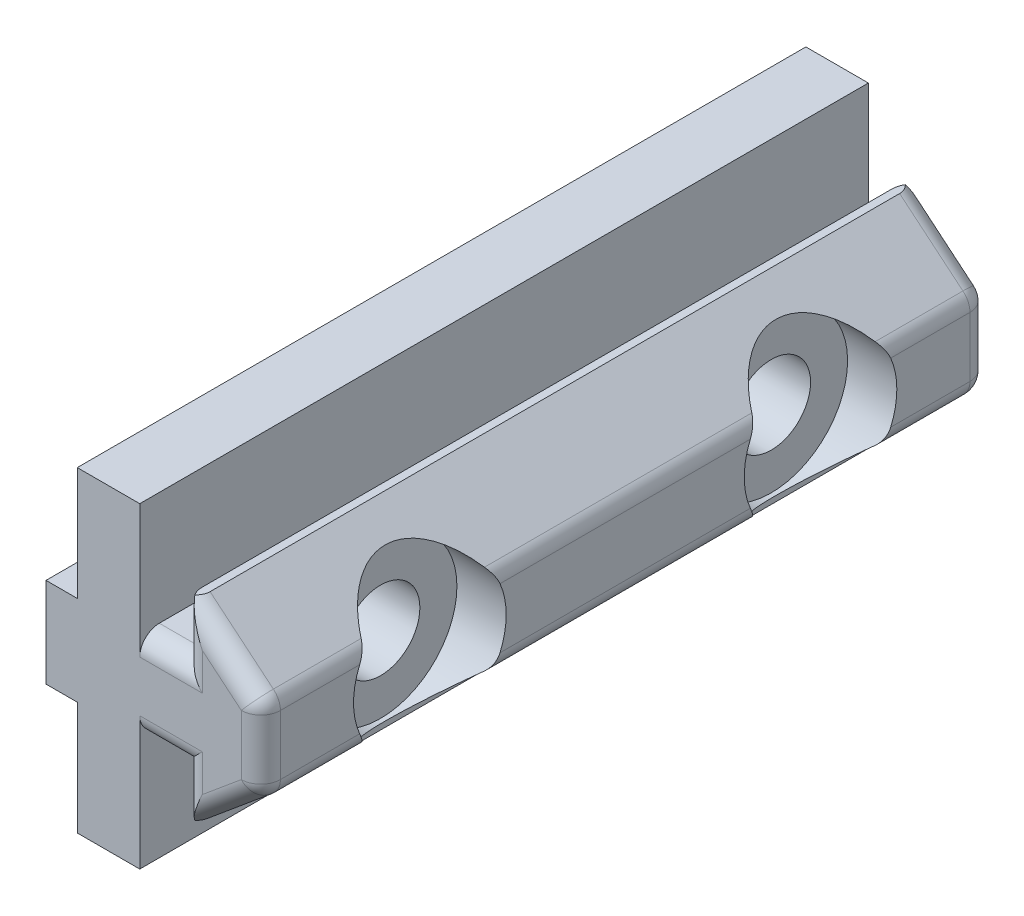
SolidWorks part; units mm, degrees
ref_plane "Front Plane" through (0, 0, 0) normal (0, 0, 1) x (1, 0, 0)
ref_plane "Top Plane" through (0, 0, 0) normal (0, 1, 0) x (1, 0, 0)
ref_plane "Right Plane" through (0, 0, 0) normal (1, 0, 0) x (0, 0, -1)
ref_plane "Plane1" through (0, 0, 23.6855) normal (0, 0, 1) x (1, 0, 0)
sketch "Sketch1" plane through (0, 0, 23.6855) normal (0, 0, 1) x (1, 0, 0)
  line L0 (3.302, 6.35) -> (-4.064, 6.35)
  line L1 (-4.064, 6.35) -> (-4.064, -6.35)
  line L2 (-4.064, -6.35) -> (3.302, -6.35)
  line L3 (3.302, -6.35) -> (7.874, -2.54)
  line L4 (7.874, -2.54) -> (7.874, 2.54)
  line L5 (7.874, 2.54) -> (3.302, 6.35)
extrude "Boss-Extrude1" add sketch "Sketch1" against normal blind 47.371
sketch "Sketch2" plane through (0, 0, 23.6855) normal (0, 0, 1) x (1, 0, 0)
  line L0 (-4.064, 6.35) -> (-4.064, 2.921)
  line L1 (-4.064, 2.921) -> (2.794, 2.921)
  line L2 (2.794, 2.921) -> (2.794, 6.35)
  line L3 (2.794, 6.35) -> (-4.064, 6.35)
extrude "Cut-Extrude1" cut sketch "Sketch2" against normal through all
sketch "Sketch3" plane through (0, 2.921, 0) normal (0, 1, 0) x (-1, 0, 0)
  line L0 (4.064, -23.6855) -> (0, -23.6855)
  line L1 (0, -23.6855) -> (0, 23.6855)
  line L2 (0, 23.6855) -> (4.064, 23.6855)
  line L3 (4.064, 23.6855) -> (4.064, -23.6855)
extrude "Boss-Extrude2" add sketch "Sketch3" along normal blind 7.366
sketch "Sketch4" plane through (0, 0, 23.6855) normal (0, 0, 1) x (1, 0, 0)
  line L0 (-4.064, -6.35) -> (2.794, -6.35)
  line L1 (2.794, -6.35) -> (2.794, -2.921)
  line L2 (2.794, -2.921) -> (-4.064, -2.921)
  line L3 (-4.064, -2.921) -> (-4.064, -6.35)
extrude "Cut-Extrude2" cut sketch "Sketch4" against normal through all
sketch "Sketch5" plane through (0, -2.921, 0) normal (0, -1, 0) x (1, 0, 0)
  line L0 (0, -23.6855) -> (-4.064, -23.6855)
  line L1 (-4.064, -23.6855) -> (-4.064, 23.6855)
  line L2 (-4.064, 23.6855) -> (0, 23.6855)
  line L3 (0, 23.6855) -> (0, -23.6855)
extrude "Boss-Extrude3" add sketch "Sketch5" along normal blind 7.366
hole_wizard "#3 Clearance Hole1" positions "Sketch7" profile "Sketch6" hole size "#3" standard "ANSI Inch"
sketch "Sketch7" plane through (-4.064, 0, 0) normal (-1, 0, 0) x (0, 0, 1)
  point P0 (12.7, 0)
  point P1 (-12.7, 0)
sketch "Sketch6" plane through (-4.064, 0, 12.7) normal (0, 1, 0) x (0, 0, 1)
  line L0 (0, 0) -> (0, 11.938)
  line L1 (0, 11.938) -> (1.3843, 11.938)
  line L2 (1.3843, 11.938) -> (1.3843, 0)
  line L5 (1.3843, 0) -> (0, 0)
  line L11 (0, -6.35) -> (0, 107.95) construction
  dimension "Thru Hole Dia." = 2.7686
  dimension "Thru Hole Depth" = 11.938
sketch "Sketch9" plane through (0, 0, 23.6855) normal (0, 0, 1) x (1, 0, 0)
  line L0 (-4.064, 10.287) -> (-4.064, -10.287) construction
  line L1 (-4.064, 2.921) -> (-6.096, 2.921)
  line L2 (-4.064, 2.921) -> (-4.064, -2.921)
  line L3 (-4.064, -2.921) -> (-6.096, -2.921)
  line L4 (-6.096, 2.921) -> (-6.096, -2.921)
  line L8 (0, 2.921) -> (2.794, 2.921) construction
  line L9 (2.794, -2.921) -> (0, -2.921) construction
  dimension "D1" = 2.032
  dimension "D2" = 5.842
extrude "Boss-Extrude4" add sketch "Sketch9" against normal through all
sketch "Sketch10" plane through (-4.064, 0, 0) normal (1, 0, 0) x (0, 0, -1)
  line L0 (-12.7, 1.3843) -> (-12.7, -1.3843) construction
  circle A0 centre (-12.7, 0) radius 1.3843 construction
  circle A1 centre (-12.7, 0) radius 1.3843 construction
  circle A2 centre (-12.7, 0) radius 1.3843
extrude "Cut-Extrude3" cut sketch "Sketch10" against normal blind 2.54
sketch "Sketch11" plane through (-4.064, 0, 0) normal (1, 0, 0) x (0, 0, -1)
  line L0 (12.7, 1.3843) -> (12.7, -1.3843) construction
  circle A0 centre (12.7, 0) radius 1.3843 construction
  circle A1 centre (12.7, 0) radius 1.3843 construction
  circle A2 centre (12.7, 0) radius 1.3843
extrude "Cut-Extrude4" [suppressed] cut sketch "Sketch11" against normal through all
sketch "Sketch12" plane through (7.874, 0, 0) normal (1, 0, 0) x (0, 0, -1)
  line L0 (-12.7, 1.3843) -> (-12.7, -1.3843) construction
  line L1 (12.7, 1.3843) -> (12.7, -1.3843) construction
  circle A0 centre (-12.7, 0) radius 1.3843 construction
  circle A1 centre (12.7, 0) radius 1.3843 construction
  point P5 (-12.7, 0)
  point P11 (12.7, 0)
  point P12 (0, 0)
  point P13 (0, 0)
hole_wizard "CBORE for #10 Button Head Cap Screw1" positions "Sketch13" profile "Sketch14" counterbore size "#10" standard "ANSI Inch" end condition through all
sketch "Sketch13" plane through (7.874, 0, 0) normal (1, 0, 0) x (0, 0, -1)
  point P0 (-12.7, 0)
  point P3 (12.7, 0)
sketch "Sketch14" plane through (7.874, 0, 12.7) normal (0, 1, 0) x (0, 0, -1)
  line L0 (0, 0) -> (0, 13.97)
  line L1 (0, 13.97) -> (2.5527, 13.97)
  line L3 (2.5527, 13.97) -> (2.5527, 3.2004)
  line L4 (2.5527, 3.2004) -> (4.9606, 3.2004)
  line L5 (4.9606, 3.2004) -> (4.9606, 0)
  line L7 (4.9606, 0) -> (0, 0)
  line L11 (0, -6.35) -> (0, 107.95) construction
  dimension "Thru Hole Dia." = 5.1054
  dimension "Thru Hole Depth" = 13.97
  dimension "C'Bore Dia." = 9.9212
  dimension "C'Bore Depth" = 3.2004
fillet "Fillet1" radius 1.27 6 edges at (7.874, -2.54, 20.3233) (7.874, -2.54, -20.3233) (7.874, -2.54, 0) (7.874, 2.54, 20.3233) (7.874, 2.54, 0) (7.874, 2.54, -20.3233)
fillet "Fillet3" radius 1.27 9 edges at (5.3595, -4.6354, -23.6855) (7.7541, -2.4838, -23.6855) (5.3595, 4.6354, -23.6855) (7.7541, 2.4838, -23.6855) (1.397, -2.921, -23.6855) (1.397, 2.921, -23.6855) (2.794, 4.6355, -23.6855) (2.794, -4.6355, -23.6855) (7.874, 0, -23.6855)
fillet "Fillet5" radius 1.27 9 edges at (5.3595, -4.6354, 23.6855) (7.7541, -2.4838, 23.6855) (5.3595, 4.6354, 23.6855) (7.7541, 2.4838, 23.6855) (2.794, 4.6355, 23.6855) (1.397, 2.921, 23.6855) (1.397, -2.921, 23.6855) (2.794, -4.6355, 23.6855) (7.874, 0, 23.6855)
